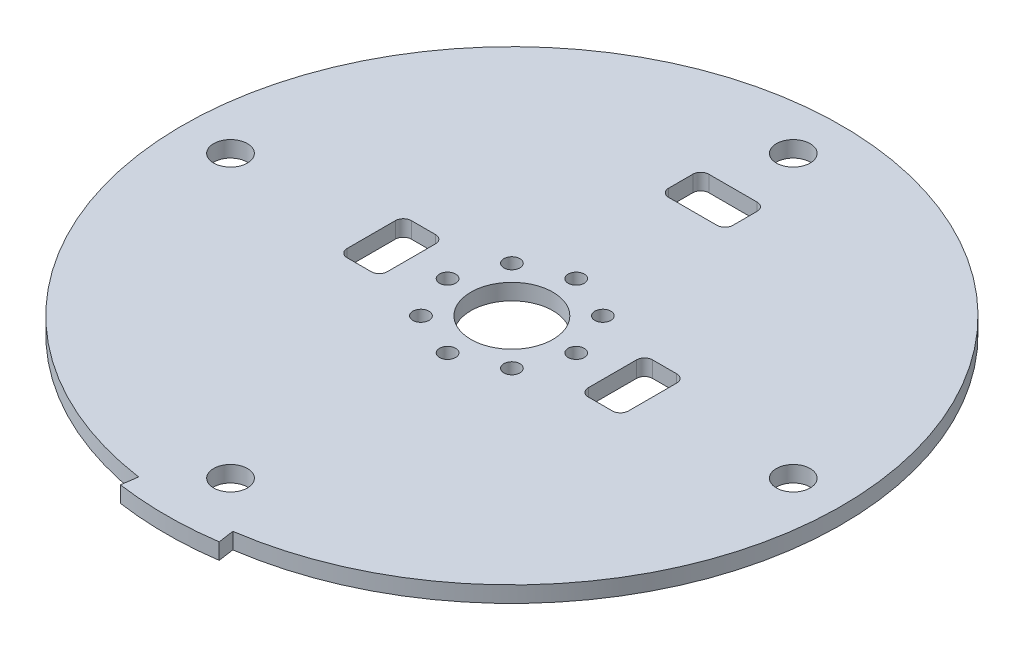
SolidWorks part; units mm, degrees
note: The reader was unsure of these and kept them because the rebuilt part matched: thickness of "基体-法兰1", "钣金6", "钣金7".
ref_plane "前视基准面" through (0, 0, 0) normal (0, 0, 1) x (1, 0, 0)
ref_plane "上视基准面" through (0, 0, 0) normal (0, 1, 0) x (1, 0, 0)
ref_plane "右视基准面" through (0, 0, 0) normal (1, 0, 0) x (0, 0, -1)
sketch "草图1" plane through (0, 0, 0) normal (0, 1, 0) x (1, 0, 0)
  line L0 (0, 41) -> (0, -82) construction
  line L1 (-6.1406, -42.5593) -> (-5.855, -40.5798)
  line L2 (6.1492, -42.5581) -> (5.8632, -40.5786)
  arc A0 (5.8632, -40.5786) -> (-5.855, -40.5798) centre (0, 0) ccw
  arc A1 (-6.1406, -42.5593) -> (6.1492, -42.5581) centre (0, 0) ccw
  dimension "D1" = 82
  dimension "D2" = 43
base flange "基体-法兰1" sketch "草图1" thickness 2 reverse thickness direction no parameters "D1"=0.7366
sketch "草图6" plane through (0, 0, 0) normal (0, 1, 0) x (1, 0, 0)
  line L0 (0, 41) -> (0, -41) construction
  line L6 (4, 22.5) -> (-4, 22.5)
  line L11 (-41, 0) -> (41, 0) construction
  line L17 (4, 22.5) -> (4, 27.5)
  line L18 (4, 27.5) -> (-4, 27.5)
  line L22 (12.5, 4) -> (17.5, 4)
  line L23 (-12.5, -4) -> (-17.5, -4)
  line L24 (-12.5, -4) -> (-12.5, 4)
  line L25 (-12.5, 4) -> (-17.5, 4)
  line L26 (-17.5, -4) -> (-17.5, 4)
  line L27 (-12.5, -4) -> (-17.5, 4) construction
  line L28 (-12.5, 4) -> (-17.5, -4) construction
  line L29 (17.5, -4) -> (17.5, 4)
  line L30 (12.5, -4) -> (17.5, -4)
  line L31 (12.5, -4) -> (12.5, 4)
  line L32 (-4, 22.5) -> (-4, 27.5)
  line L33 (4, 22.5) -> (-4, 27.5) construction
  line L34 (4, 27.5) -> (-4, 22.5) construction
  circle A0 centre (0, 35) radius 2.1
  circle A1 centre (0, 0) radius 41 construction
  circle A2 centre (35, 0) radius 2.1
  circle A3 centre (0, -35) radius 2.1
  circle A4 centre (-35, 0) radius 2.1
  circle A5 centre (0, 0) radius 5.1
  circle A6 centre (0, 0) radius 8 construction
  circle A7 centre (0, 8) radius 1
  circle A8 centre (5.6569, 5.6569) radius 1
  circle A9 centre (8, 0) radius 1
  circle A10 centre (5.6569, -5.6569) radius 1
  circle A11 centre (0, -8) radius 1
  circle A12 centre (-5.6569, -5.6569) radius 1
  circle A13 centre (-8, 0) radius 1
  circle A14 centre (-5.6569, 5.6569) radius 1
  point P13 (0, 0)
  point P17 (0, 0)
  point P18 (0, 25)
  point P34 (0, 0)
  point P40 (0, 0)
  point P41 (0, 0)
  point P42 (0, 0)
  point P46 (0, 0)
  point P49 (-15, 0)
  dimension "D1" = 4.2
  dimension "D4" = 10.2
  dimension "D5" = 16
  dimension "D6" = 2
  dimension "D10" = 8
  dimension "D2" = 35
  dimension "D8" = 25
  dimension "D9" = 5
  dimension "D12" = 15
  dimension "D16" = 8
  dimension "D17" = 5
  dimension "D3" = 4
  dimension "D7" = 8
extrude "切除-拉伸1" cut sketch "草图6" against normal up to next normal cut yes
fillet "圆角1" radius 1 12 edges at (17.5, -1, -4) (12.5, -1, -4) (12.5, -1, 4) (17.5, -1, 4) (-12.5, -1, 4) (-17.5, -1, 4) (-17.5, -1, -4) (-12.5, -1, -4) (-4, -1, -27.5) (-4, -1, -22.5) (4, -1, -22.5) (4, -1, -27.5)
sketch "折弯-线1" plane through (0, 0, 0) normal (0, 1, 0) x (1, 0, 0)
sketch "边界框1" plane through (0, 0, 0) normal (0, 1, 0) x (1, 0, 0)
sheet metal parameters "钣金6" thickness 2 parameters "D1"=0.7366
flat pattern "平板型式6" [suppressed]
sketch "折弯-线2" plane through (0, 0, 0) normal (0, 1, 0) x (1, 0, 0)
sketch "边界框2" [suppressed] plane through (0, 0, 0) normal (0, 1, 0) x (1, 0, 0)
sheet metal parameters "钣金7" thickness 2 parameters "D1"=0.7366, "D7"=3
flat pattern "平板型式6"
sketch "折弯-线2" plane through (0, 0, 0) normal (0, 1, 0) x (1, 0, 0)
sketch "边界框2" [suppressed] plane through (0, 0, 0) normal (0, 1, 0) x (1, 0, 0)
